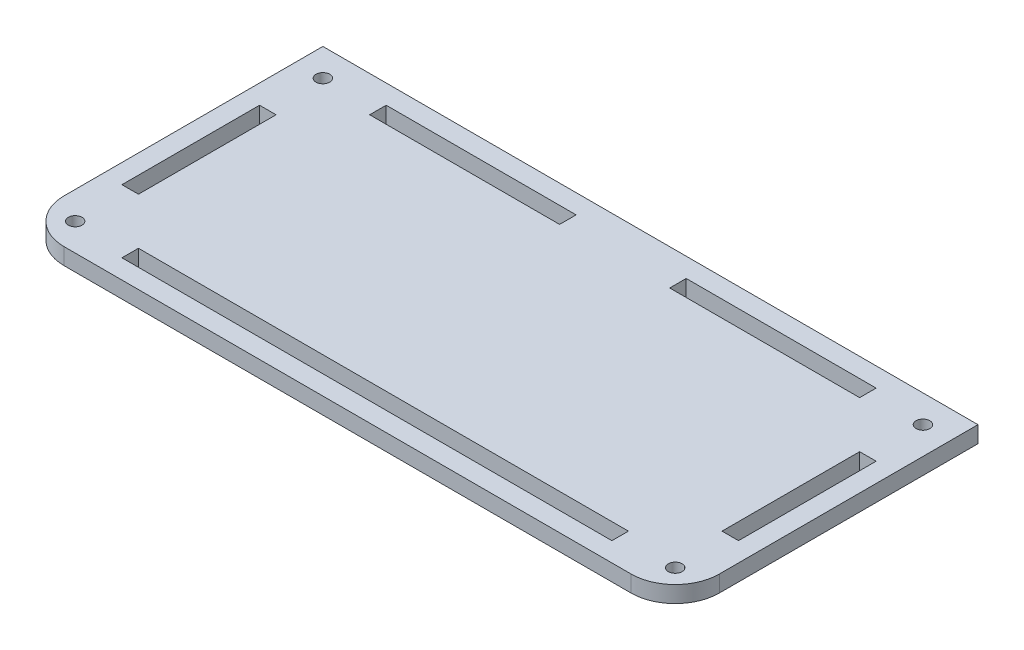
SolidWorks part; units mm, degrees
material "PVC rigido"
ref_plane "Piano frontale" through (0, 0, 0) normal (0, 0, 1) x (1, 0, 0)
ref_plane "Piano superiore" through (0, 0, 0) normal (0, 1, 0) x (1, 0, 0)
ref_plane "Piano destro" through (0, 0, 0) normal (1, 0, 0) x (0, 0, -1)
sketch "Schizzo1" plane through (0, 0, 0) normal (0, 1, 0) x (1, 0, 0)
  line L1 (-59.5, -27.5) -> (59.5, -27.5)
  line L2 (-59.5, -27.5) -> (-59.5, 27.5)
  line L3 (-59.5, 27.5) -> (59.5, 27.5)
  line L4 (59.5, -27.5) -> (59.5, 27.5)
  line L5 (-59.5, -27.5) -> (59.5, 27.5) construction
  line L6 (-59.5, 27.5) -> (59.5, -27.5) construction
  line L7 (67.5, 0) -> (59.5, 0) construction
  line L8 (67.5, -27.5) -> (67.5, -18) construction
  line L9 (-59.5, 0) -> (-67.5, 0) construction
  line L10 (-67.5, 21.5) -> (-67.5, 12) construction
  point P0 (0, 0)
  dimension "D1" = 8
  dimension "D2" = 55
extrude "Estrusione-Estrusione1" add sketch "Schizzo1" along normal blind 3
hole_wizard "Foro filettato M3x0.5-1" positions "Schizzo3" profile "Schizzo2" tap size "M3x0.5" standard "Ansi Metric" end condition through all
sketch "Schizzo3" plane through (0, 3, 0) normal (0, 1, 0) x (1, 0, 0)
  line L16 (54.5, -22.5) -> (54.5, 22.5)
  line L17 (54.5, 22.5) -> (-54.5, 22.5)
  line L18 (-54.5, 22.5) -> (-54.5, -22.5)
  line L19 (-54.5, -22.5) -> (54.5, -22.5)
  line L20 (54.5, -22.5) -> (54.5, 22.5) construction
  line L21 (54.5, 22.5) -> (-54.5, 22.5) construction
  line L22 (-54.5, 22.5) -> (-54.5, -22.5) construction
  line L23 (-54.5, -22.5) -> (54.5, -22.5) construction
  point P0 (-54.5, -22.5)
  point P2 (54.5, -22.5)
  point P4 (54.5, 22.5)
  point P6 (-54.5, 22.5)
  dimension "D1" = 5
sketch "Schizzo2" plane through (-54.5, 3, 22.5) normal (1, 0, 0) x (0, 0, 1)
  line L0 (0, 0) -> (0, 3)
  line L1 (0, 3) -> (1.25, 3)
  line L2 (1.25, 3) -> (1.25, 0)
  line L5 (1.25, 0) -> (0, 0)
  line L11 (0, -6.35) -> (0, 107.95) construction
  dimension "Thru Tap Drill Dia." = 2.5
  dimension "Thru Tap Drill Depth" = 3
cosmetic thread "Filettatura del foro1" parameters "D2"=3
cosmetic thread "Filettatura del foro2" parameters "D2"=3
cosmetic thread "Filettatura del foro3" parameters "D2"=3
cosmetic thread "Filettatura del foro4" parameters "D2"=3
sketch "Schizzo4" plane through (0, 3, 0) normal (0, 1, 0) x (1, 0, 0)
  line L0 (-54.5, -22.5) -> (-44.5, -22.5) construction
  line L1 (-44.5, -22.5) -> (44.5, -22.5) construction
  line L2 (44.5, -22.5) -> (54.5, -22.5) construction
  line L3 (54.5, -22.5) -> (54.5, -12.5) construction
  line L4 (54.5, -12.5) -> (54.5, 12.5) construction
  line L5 (54.5, 12.5) -> (54.5, 22.5) construction
  line L6 (-54.5, -22.5) -> (-54.5, -12.5) construction
  line L7 (-54.5, -12.5) -> (-54.5, 12.5) construction
  line L8 (-54.5, 12.5) -> (-54.5, 22.5) construction
  line L10 (-44.5, -24) -> (44.5, -24)
  line L11 (-44.5, -24) -> (-44.5, -21)
  line L12 (-44.5, -21) -> (44.5, -21)
  line L13 (44.5, -24) -> (44.5, -21)
  line L14 (53, 12.5) -> (56, 12.5)
  line L15 (53, 12.5) -> (53, -12.5)
  line L16 (53, -12.5) -> (56, -12.5)
  line L17 (56, 12.5) -> (56, -12.5)
  line L18 (-53, -12.5) -> (-56, -12.5)
  line L19 (-53, -12.5) -> (-53, 12.5)
  line L20 (-53, 12.5) -> (-56, 12.5)
  line L21 (-56, -12.5) -> (-56, 12.5)
  dimension "D1" = 10
  dimension "D2" = 3
extrude "Taglio-Estrusione1" cut sketch "Schizzo4" against normal through all
fillet "Raccordo1" radius 8 2 edges at (-59.5, 1.5, 27.5) (59.5, 1.5, 27.5)
sketch "Schizzo5" plane through (0, 3, 0) normal (0, 1, 0) x (1, 0, 0)
  line L0 (44.5, -24) -> (44.5, -21) construction
  line L1 (44.5, 24) -> (10, 24)
  line L2 (44.5, 24) -> (44.5, 21)
  line L3 (44.5, 21) -> (10, 21)
  line L4 (-44.5, 24) -> (-44.5, 21)
  line L6 (0, -21) -> (0, 0) construction
  line L7 (44.5, -21) -> (-44.5, -21) construction
  line L8 (0, 0) -> (0, 21) construction
  line L9 (10, 21) -> (10, 24)
  line L10 (-10, 21) -> (-10, 24)
  line L11 (-10, 24) -> (-44.5, 24)
  line L12 (-10, 21) -> (-44.5, 21)
  line L13 (10, 21) -> (-10, 21) construction
  dimension "D1" = 20
extrude "Taglio-Estrusione2" cut sketch "Schizzo5" against normal blind 10
